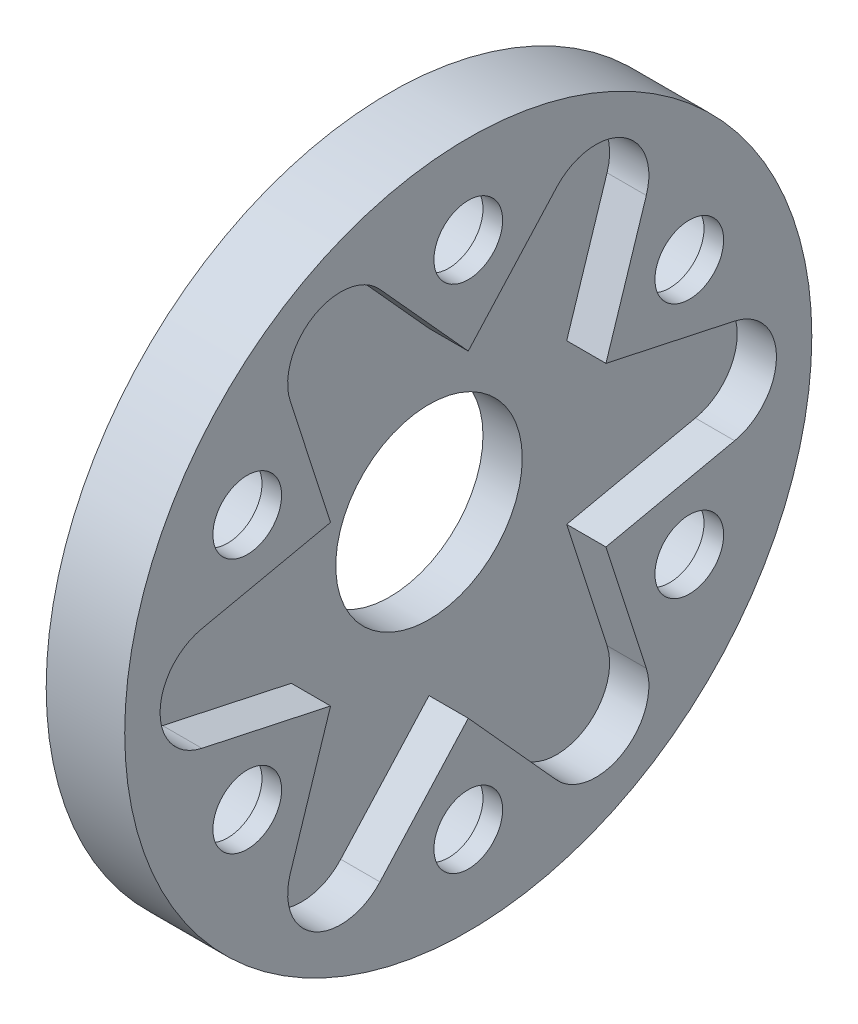
SolidWorks part; units mm, degrees
ref_plane "Front Plane" through (0, 0, 0) normal (0, 0, 1) x (1, 0, 0)
ref_plane "Top Plane" through (0, 0, 0) normal (0, 1, 0) x (1, 0, 0)
ref_plane "Right Plane" through (0, 0, 0) normal (1, 0, 0) x (0, 0, -1)
sketch "Sketch1" plane through (0, 0, 0) normal (1, 0, 0) x (0, 0, -1)
  circle A0 centre (0, 0) radius 17.5
  circle A1 centre (0, 0) radius 4.75
  dimension "D1" = 35
  dimension "D2" = 9.5
extrude "Boss-Extrude1" add sketch "Sketch1" along normal blind 4
sketch "Sketch2" plane through (4, 0, 0) normal (1, 0, 0) x (0, 0, -1)
  line L0 (0, 0) -> (13, 0) construction
  line L1 (13.5258, 2.4441) -> (3.9686, 4.5) construction
  line L2 (13.5258, -2.4441) -> (3.9686, -4.5) construction
  line L3 (8.8795, -10.4916) -> (5.8814, -1.1869) construction
  line L4 (4.6462, -12.9357) -> (-1.9128, -5.6869) construction
  line L5 (-4.6462, -12.9357) -> (1.9128, -5.6869) construction
  line L6 (-8.8795, -10.4916) -> (-5.8814, -1.1869) construction
  line L7 (-13.5258, -2.4441) -> (-3.9686, -4.5) construction
  line L8 (-13.5258, 2.4441) -> (-3.9686, 4.5) construction
  line L9 (-8.8795, 10.4916) -> (-5.8814, 1.1869) construction
  line L10 (-4.6462, 12.9357) -> (1.9128, 5.6869) construction
  line L11 (4.6462, 12.9357) -> (-1.9128, 5.6869) construction
  line L12 (8.8795, 10.4916) -> (5.8814, 1.1869) construction
  line L13 (13.5678, -2.6396) -> (7.0139, -4.0495)
  line L14 (13.5678, 2.6396) -> (7.0139, 4.0495)
  line L15 (4.4979, 13.0699) -> (0, 8.099)
  line L16 (9.0699, 10.4303) -> (7.0139, 4.0495)
  line L17 (-9.0699, 10.4303) -> (-7.0139, 4.0495)
  line L18 (-4.4979, 13.0699) -> (0, 8.099)
  line L19 (-13.5678, -2.6396) -> (-7.0139, -4.0495)
  line L20 (-13.5678, 2.6396) -> (-7.0139, 4.0495)
  line L21 (-4.4979, -13.0699) -> (0, -8.099)
  line L22 (-9.0699, -10.4303) -> (-7.0139, -4.0495)
  line L23 (9.0699, -10.4303) -> (7.0139, -4.0495)
  line L24 (4.4979, -13.0699) -> (0, -8.099)
  line L25 (-9.0699, 10.4303) -> (-6.0718, 1.1256) construction
  line L26 (-9.0699, -10.4303) -> (-6.0718, -1.1256) construction
  line L27 (-13.5678, 2.6396) -> (-4.0107, 4.6955) construction
  line L28 (4.4979, -13.0699) -> (-2.0611, -5.8211) construction
  line L29 (-13.5678, -2.6396) -> (-4.0107, -4.6955) construction
  line L30 (-4.4979, -13.0699) -> (2.0611, -5.8211) construction
  line L31 (13.5678, -2.6396) -> (4.0107, -4.6955) construction
  line L32 (9.0699, 10.4303) -> (6.0718, 1.1256) construction
  line L33 (9.0699, -10.4303) -> (6.0718, -1.1256) construction
  line L34 (13.5678, 2.6396) -> (4.0107, 4.6955) construction
  line L35 (-4.4979, 13.0699) -> (2.0611, 5.8211) construction
  line L36 (4.4979, 13.0699) -> (-2.0611, 5.8211) construction
  circle A0 centre (0, 0) radius 6 construction
  circle A1 centre (0, 0) radius 4.75 construction
  arc A2 (13.5258, 2.4441) -> (13.5258, -2.4441) centre (13, 0) cw construction
  arc A3 (8.8795, -10.4916) -> (4.6462, -12.9357) centre (6.5, -11.2583) cw construction
  arc A4 (-4.6462, -12.9357) -> (-8.8795, -10.4916) centre (-6.5, -11.2583) cw construction
  arc A5 (-13.5258, -2.4441) -> (-13.5258, 2.4441) centre (-13, 0) cw construction
  arc A6 (-8.8795, 10.4916) -> (-4.6462, 12.9357) centre (-6.5, 11.2583) cw construction
  arc A7 (4.6462, 12.9357) -> (8.8795, 10.4916) centre (6.5, 11.2583) cw construction
  arc A8 (13.5678, 2.6396) -> (13.5678, -2.6396) centre (13, 0) cw
  arc A9 (4.4979, 13.0699) -> (9.0699, 10.4303) centre (6.5, 11.2583) cw
  arc A10 (-9.0699, 10.4303) -> (-4.4979, 13.0699) centre (-6.5, 11.2583) cw
  arc A11 (-13.5678, -2.6396) -> (-13.5678, 2.6396) centre (-13, 0) cw
  arc A12 (-4.4979, -13.0699) -> (-9.0699, -10.4303) centre (-6.5, -11.2583) cw
  arc A13 (9.0699, -10.4303) -> (4.4979, -13.0699) centre (6.5, -11.2583) cw
  point P37 (0, 0)
  dimension "D1" = 12
  dimension "D2" = 9.5
  dimension "D4" = 2.5
  dimension "D3" = 13
  dimension "D5" = 9
  dimension "D6" = 0
  dimension "D8" = 0.2
  dimension "D9" = 0.2
  dimension "D10" = 0.2
  dimension "D7" = 6
extrude "Cut-Extrude1" cut sketch "Sketch2" against normal offset from surface (2 mm away) 2 up to face at (0, 0, -17.5)
sketch "Sketch3" plane through (4, 0, 0) normal (1, 0, 0) x (0, 0, -1)
  circle A0 centre (0, 13) radius 1.75
  circle A1 centre (11.2583, 6.5) radius 1.75
  circle A2 centre (11.2583, -6.5) radius 1.75
  circle A3 centre (0, -13) radius 1.75
  circle A4 centre (-11.2583, -6.5) radius 1.75
  circle A5 centre (-11.2583, 6.5) radius 1.75
  point P16 (0, 0)
  dimension "D1" = 13
  dimension "D2" = 3.5
  dimension "D3" = 6
extrude "Cut-Extrude2" cut sketch "Sketch3" against normal through all
sketch "Sketch4" plane through (0, 0, 0) normal (-1, 0, 0) x (0, 0, 1)
  circle A0 centre (-11.2583, 6.5) radius 3
  circle A1 centre (0, 13) radius 3
  circle A2 centre (11.2583, 6.5) radius 3
  circle A3 centre (11.2583, -6.5) radius 3
  circle A4 centre (0, -13) radius 3
  circle A5 centre (-11.2583, -6.5) radius 3
  point P16 (0, 0)
  dimension "D1" = 6
extrude "Cut-Extrude3" cut sketch "Sketch4" against normal blind 3
